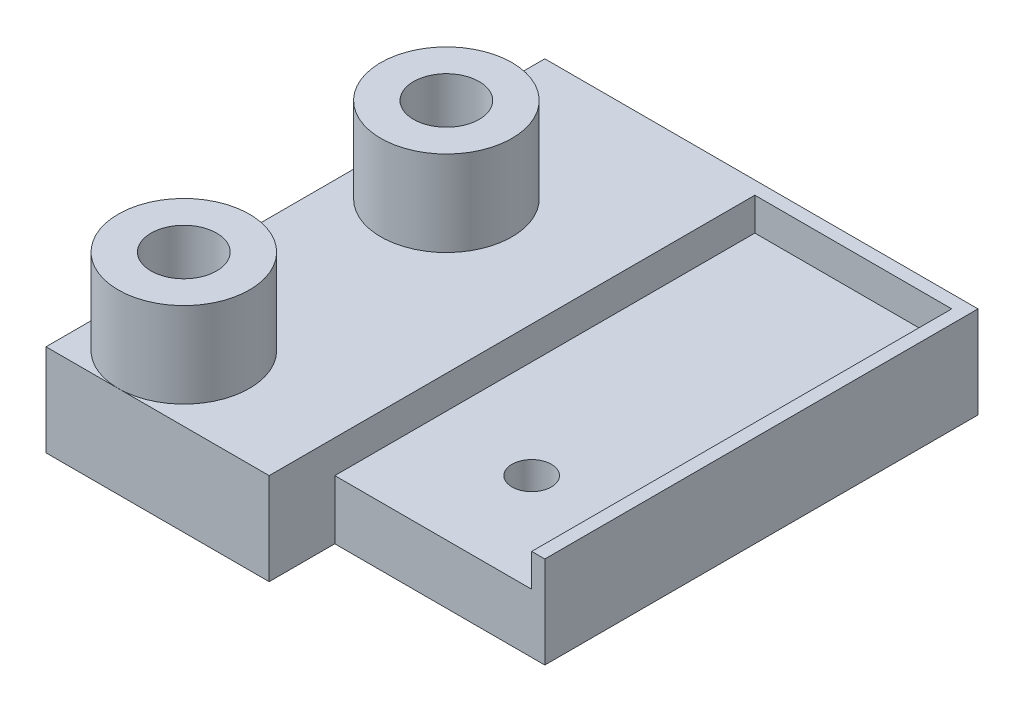
SolidWorks part; units mm, degrees
ref_plane "Front" through (0, 0, 0) normal (0, 0, 1) x (1, 0, 0)
ref_plane "Top" through (0, 0, 0) normal (0, 1, 0) x (1, 0, 0)
ref_plane "Right" through (0, 0, 0) normal (1, 0, 0) x (0, 0, -1)
sketch "Sketch1" plane through (0, 0, 0) normal (0, 1, 0) x (1, 0, 0)
  line L1 (0, 0) -> (-33, 0)
  line L2 (0, 0) -> (0, 33)
  line L3 (0, 33) -> (-33, 33)
  line L4 (-33, 0) -> (-33, 33)
  dimension "D1" = 33
  dimension "D2" = 33
extrude "Boss-Extrude1" add sketch "Sketch1" along normal blind 7
sketch "Sketch2" plane through (0, 7, 0) normal (0, 1, 0) x (1, 0, 0)
  line L0 (0, 0) -> (0, 33) construction
  line L1 (-1, 32) -> (-16, 32)
  line L2 (-1, 32) -> (-1, 0)
  line L3 (-1, 0) -> (-16, 0)
  line L4 (-16, 32) -> (-16, 0)
  line L5 (0, 33) -> (-33, 33) construction
  dimension "D1" = 1
  dimension "D2" = 15
  dimension "D3" = 32
  dimension "D4" = 1
extrude "Cut-Extrude1" cut sketch "Sketch2" against normal blind 2.5
sketch "Sketch4" plane through (0, 7, 0) normal (0, 1, 0) x (1, 0, 0)
  line L0 (-33, 33) -> (-33, 0) construction
  line L1 (-16, 0) -> (-33, 0)
  line L2 (-16, 0) -> (-16, -5)
  line L3 (-16, -5) -> (-33, -5)
  line L4 (-33, 0) -> (-33, -5)
  dimension "D1" = 5
extrude "Boss-Extrude3" add sketch "Sketch4" against normal up to surface (7 mm away) up to face at (-16.5, 0, -16.5)
sketch "Sketch3" plane through (0, 7, 0) normal (0, 1, 0) x (1, 0, 0)
  line L0 (-1, 32) -> (-16, 32) construction
  line L1 (-1, 32) -> (-16, 32) construction
  line L2 (-8.5, 32) -> (-8.5, 7.5) construction
  line L4 (-33, -5) -> (-16, -5) construction
  circle A0 centre (-8.5, 7.5) radius 1.5
  circle A1 centre (-27.5, 20) radius 2.5
  circle A2 centre (-27.5, 0) radius 2.5
  circle A3 centre (-27.5, 20) radius 5
  circle A4 centre (-27.5, 0) radius 5
  point P0 (-27.5, 20)
  point P3 (-8.5, 32)
  dimension "D4" = 3
  dimension "D5" = 5
  dimension "D1" = 19
  dimension "D2" = 12
  dimension "D3" = 24.5
  dimension "D6" = 20
extrude "Boss-Extrude4" add sketch "Sketch3" along normal blind 6.5 contours A3 A1 | A4 A2 region at (-32.3586, 7, -20) region at (-32.3586, 7, 0)
extrude "Cut-Extrude4" cut sketch "Sketch3<3>" against normal through all both and the other way through all contours A1 | A2 | A0 region at (-8.5, 7, -7.5) region at (-27.5, 7, -20) region at (-27.5, 7, 0)
sketch "Sketch3<3>" plane through (0, 7, 0) normal (0, 1, 0) x (1, 0, 0) same geometry as "Sketch3"
